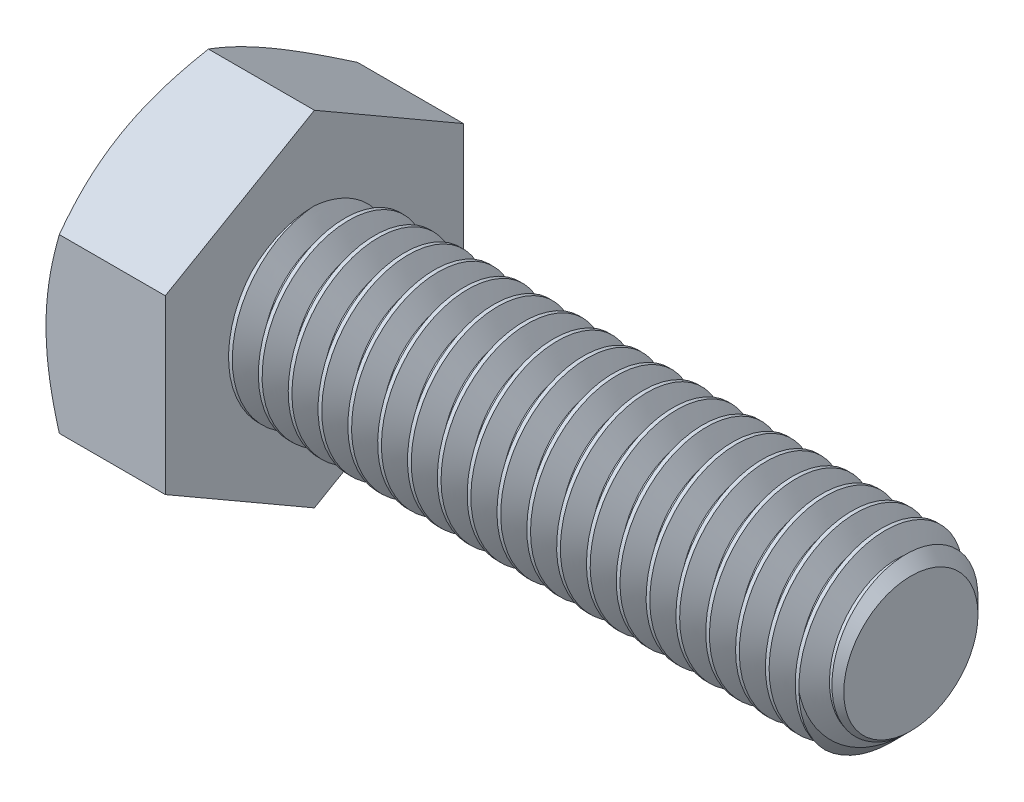
SolidWorks part; units mm, degrees
ref_plane "Front Plane" through (0, 0, 0) normal (0, 0, 1) x (1, 0, 0)
ref_plane "Top Plane" through (0, 0, 0) normal (0, 1, 0) x (1, 0, 0)
ref_plane "Right Plane" through (0, 0, 0) normal (1, 0, 0) x (0, 0, -1)
sketch "Sketch1" plane through (0, 0, 0) normal (0, 0, 1) x (1, 0, 0)
  line L0 (-12, 0) -> (12, 0) construction
  line L1 (-8, 5) -> (-8, -5) construction
  line L2 (-12, 5) -> (-12, -5) construction
  line L3 (12, 3) -> (12, -3) construction
  point P8 (8.5, -3)
  dimension "Thread Dia" = 6
  dimension "Hex" = 10
  dimension "Head Ht" = 4
  dimension "Length" = 20
  dimension "D1" = 3.5
ref_plane "Plane2" through (12, 0, 0) normal (1, 0, 0) x (0, 0, -1)
sketch "Sketch2" plane through (12, 0, 0) normal (1, 0, 0) x (0, 0, -1)
  circle A0 centre (0, 0) radius 3
extrude "Boss-Extrude1" add sketch "Sketch2" against normal up to vertex (20 mm away) up to point (-8, -5, 0)
sketch "Sketch4" plane through (12, 0, 0) normal (1, 0, 0) x (0, 0, -1)
  circle A1 centre (0, 0) radius 3
  circle A2 centre (0, 0) radius 3
  dimension "D1" = 0
curve "Helix/Spiral1" pitch 1 height 21 turns 21 parameters "Pitch"=1
chamfer "Chamfer1" distance 0.75 angle 45 1 edges at (12, 0, -3)
sketch "Sketch5" plane through (0, 0, 0) normal (0, 0, 1) x (1, 0, 0)
  line L0 (12, 3) -> (12.375, 2.3505)
  line L1 (12.375, 2.3505) -> (12.5, 2.3505)
  line L2 (12.5, 2.3505) -> (12.875, 3)
  line L3 (12, 3) -> (12.875, 3)
  line L4 (12.4375, 2.3505) -> (12.4375, 3) construction
  line L5 (12.1875, 2.6752) -> (12.6875, 2.6752) construction
  line L6 (12, -3) -> (12, 3) construction
  dimension "D1" = 60
  dimension "D2" = 0.125
  dimension "D3" = 0.5
sweep "Cut-Sweep1" cut profiles "Sketch5" path "Helix/Spiral1" align with end faces yes
sketch "Sketch3" plane through (-8, 0, 0) normal (-1, 0, 0) x (0, 0, 1)
  line L0 (0, 5) -> (0, -5) construction
  line L1 (-5, -2.8868) -> (0, -5.7735)
  line L2 (0, -5.7735) -> (5, -2.8868)
  line L3 (5, -2.8868) -> (5, 2.8868)
  line L4 (5, 2.8868) -> (0, 5.7735)
  line L5 (0, 5.7735) -> (-5, 2.8868)
  line L6 (-5, 2.8868) -> (-5, -2.8868)
  circle A0 centre (0, 0) radius 5 construction
extrude "Boss-Extrude2" add sketch "Sketch3" along normal up to vertex (4 mm away) up to point (-12, -5, 0)
sketch "Sketch6" plane through (-12, 0, 0) normal (-1, 0, 0) x (0, 0, 1)
  circle A0 centre (0, 0) radius 5 construction
  circle A1 centre (0, 0) radius 5
extrude "Cut-Extrude1" cut sketch "Sketch6" against normal through all draft 60 flip side to cut
sketch "Sketch9" plane through (0, 0, 0) normal (0, 0, 1) x (1, 0, 0)
  line L0 (-8, 3) -> (-8, 0)
  line L1 (-8, 0) -> (-39, 0)
  line L2 (-39, 0) -> (-42, 3)
  line L3 (-42, 3) -> (-8, 3)
  line L4 (-12, 0) -> (12, 0) construction
  line L5 (-8, 5) -> (-8, -5) construction
  line L6 (12, 3) -> (12, -3) construction
  dimension "D1" = 45
  dimension "MinThreadLg" = 54
revolve "Revolve1" [suppressed] add sketch "Sketch9" angle 360 about L1
equation "\"D2@Sketch5\" = \"Pitch@Helix/Spiral1\"*.125"
equation "\"D3@Sketch5\" = \"Pitch@Helix/Spiral1\"*.50"
equation "\"D3@Helix/Spiral1\" = \"Length@Sketch1\"+\"Pitch@Helix/Spiral1\""
equation "\"D1@Chamfer1\" = \"Pitch@Helix/Spiral1\"*.750"
equation "\"D1@Sketch1\" = \"Pitch@Helix/Spiral1\"*3.50"
